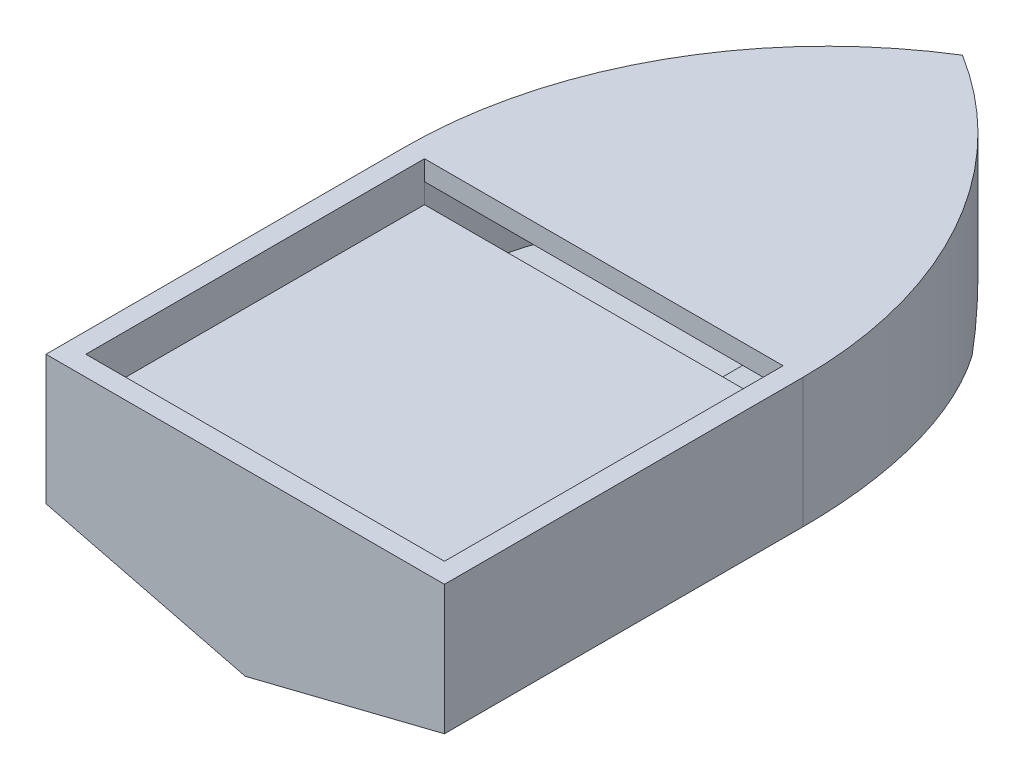
SolidWorks part; units mm, degrees
material "Custom Plastic"
ref_plane "Front Plane" through (0, 0, 0) normal (0, 0, 1) x (1, 0, 0)
ref_plane "Top Plane" through (0, 0, 0) normal (0, 1, 0) x (1, 0, 0)
ref_plane "Right Plane" through (0, 0, 0) normal (1, 0, 0) x (0, 0, -1)
sketch "Sketch2" plane through (0, 0, 0) normal (1, 0, 0) x (0, 0, -1)
  line L0 (0, 0) -> (250, 0)
  line L1 (360, 70) -> (360, 90)
  line L2 (360, 90) -> (0, 90)
  line L3 (0, 90) -> (0, 0)
  arc A0 (250, 0) -> (360, 70) centre (250, 121.4286) ccw
  dimension "D1" = 110
  dimension "D2" = 250
  dimension "D3" = 70
  dimension "D4" = 90
extrude "Boss-Extrude1" add sketch "Sketch2" against normal mid plane 200
sketch "Sketch3" plane through (0, 0, 0) normal (0, 0, 1) x (1, 0, 0)
  line L0 (100, 25) -> (-100, 25)
  line L1 (100, 90) -> (100, 0) construction
  line L2 (-100, 90) -> (-100, 0) construction
  line L3 (-100, 25) -> (0, 0)
  line L4 (-100, 0) -> (100, 0) construction
  line L5 (0, 0) -> (100, 25)
  line L6 (-100, 90) -> (100, 90) construction
  line M4 (100, 0) -> (100, 90)
  line M6 (-100, 90) -> (-100, 0)
  line M7 (-100, 0) -> (100, 0)
  dimension "D1" = 65
extrude "Cut-Extrude1" cut sketch "Sketch3" against normal through all contours L3 M6 M7 | L5 M7 M4 region at (66.6667, 8.3333, 0) region at (-66.6667, 8.3333, 0)
sketch "Sketch4" plane through (0, 90, 0) normal (0, 1, 0) x (1, 0, 0)
  line L0 (-100, 360) -> (100, 360) construction
  line L1 (100, 360) -> (100, 0) construction
  line L2 (0, 360) -> (0, 0) construction
  line L3 (-100, 180) -> (-100, 360)
  line L4 (-100, 360) -> (100, 360)
  line L5 (100, 360) -> (100, 180)
  arc A0 (0, 360) -> (100, 180) centre (-112, 180) cw
  arc A1 (0, 360) -> (-100, 180) centre (112, 180) ccw
  line M2 (100, 0) -> (100, 360)
  line M3 (100, 360) -> (-100, 360)
  line M4 (-100, 360) -> (-100, 0)
  dimension "D1" = 180
extrude "Cut-Extrude2" cut sketch "Sketch4" against normal through all contours A0 M3 M2 | A1 L4 M4 region at (71.7789, 90, -317.393) region at (-71.7789, 90, -317.393)
shell "Shell1" thickness 10 removed face at (0, 90, -149.1825)
sketch "Sketch5" plane through (0, 90, 0) normal (0, 1, 0) x (1, 0, 0)
  line L0 (-90, 180) -> (-90, 10)
  line L1 (-90, 10) -> (90, 10)
  line L2 (90, 10) -> (90, 180)
  line L3 (90, 180) -> (-90, 180)
extrude "Boss-Extrude4" add sketch "Sketch5" against normal blind 40
extrude "Cut-Extrude4" cut sketch "Sketch5<3>" against normal blind 20
sketch "Sketch5<3>" plane through (0, 90, 0) normal (0, 1, 0) x (1, 0, 0) same geometry as "Sketch5"
sketch "Sketch8" plane through (0, 90, 0) normal (0, 1, 0) x (1, 0, 0)
  line L0 (-90, 180) -> (90, 180)
  arc A0 (90, 180) -> (0, 348.1071) centre (-112, 180) ccw
  arc A1 (0, 348.1071) -> (-90, 180) centre (112, 180) ccw
extrude "Boss-Extrude5" add sketch "Sketch8" against normal blind 10
